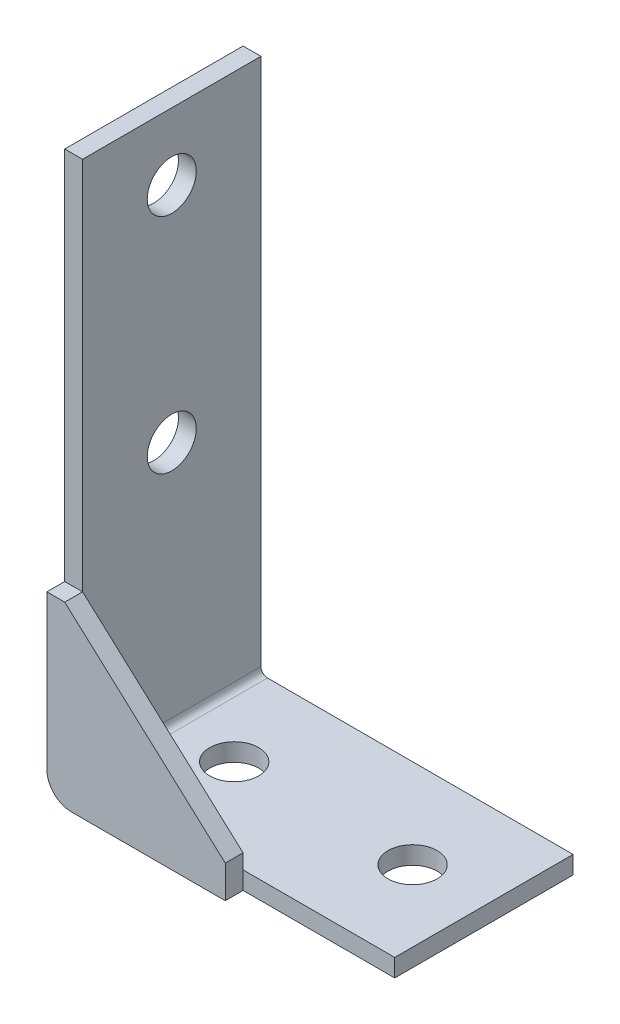
SolidWorks part; units mm, degrees
note: The reader was unsure of these and kept them because the rebuilt part matched: bend radius of "基体折弯1".
material "A3钢"
ref_plane "前视基准面" through (0, 0, 0) normal (0, 0, 1) x (1, 0, 0)
ref_plane "上视基准面" through (0, 0, 0) normal (0, 1, 0) x (1, 0, 0)
ref_plane "右视基准面" through (0, 0, 0) normal (1, 0, 0) x (0, 0, -1)
sketch "草图1" plane through (0, 0, 0) normal (0, 0, 1) x (1, 0, 0)
  line L0 (0, 60) -> (0, 0)
  line L1 (0, 0) -> (35, 0)
  dimension "D1" = 60
  dimension "D2" = 35
base flange "基体-法兰1" sketch "草图1" end condition mid plane depth 20 reverse direction no thickness 2 reverse thickness direction no bend radius 0.7366
bend "基体折弯1" bend radius 0.7366 bend angle 90 parameters "D5"=1
sketch "草图6" plane through (0, 0, 0) normal (0, 1, 0) x (1, 0, 0)
  line L0 (35, 0) -> (27, 0) construction
  line L1 (35, -10) -> (35, 10) construction
  line L2 (27, 0) -> (7, 0) construction
  dimension "D1" = 20
  dimension "D2" = 8
hole_wizard "Ø5.5 (5.5) 直径孔1" positions "3D草图1" profile "草图7" hole size "Ø5.5" standard "GB" end condition through all
sketch3d "3D草图1"
  point P0 (7, 0, 0)
  point P3 (27, 0, 0)
sketch "草图7" plane through (7, 0, 0) normal (1, 0, 0) x (0, 0, 1)
  line L0 (0, 0) -> (0, 2)
  line L1 (0, 2) -> (2.75, 2)
  line L2 (2.75, 2) -> (2.75, 0)
  line L5 (2.75, 0) -> (0, 0)
  line L11 (0, -6.35) -> (0, 107.95) construction
  dimension "通孔孔直径" = 5.5
  dimension "通孔孔深度" = 2
sketch "草图8" plane through (-2, 0, 0) normal (-1, 0, 0) x (0, 0, 1)
  line L0 (0, 60) -> (0, 52.5) construction
  line L1 (10, 60) -> (-10, 60) construction
  line L2 (0, 52.5) -> (0, 27.5) construction
  dimension "D1" = 25
  dimension "D2" = 7.5
hole_wizard "Ø5.5 (5.5) 直径孔2" positions "3D草图2" profile "草图10" hole size "Ø5.5" standard "GB" end condition through all
sketch3d "3D草图2"
  point P0 (-2, 52.5, 0)
  point P3 (-2, 27.5, 0)
sketch "草图10" plane through (-2, 52.5, 0) normal (0, 1, 0) x (0, 0, 1)
  line L0 (0, 0) -> (0, 37)
  line L1 (0, 37) -> (2.75, 37)
  line L2 (2.75, 37) -> (2.75, 0)
  line L5 (2.75, 0) -> (0, 0)
  line L11 (0, -6.35) -> (0, 107.95) construction
  dimension "通孔孔直径" = 5.5
  dimension "通孔孔深度" = 37
sketch "草图11" plane through (0, 0, 10) normal (0, 0, 1) x (1, 0, 0)
  line L0 (18, -2) -> (18, 1.6564)
  line L3 (18, 1.6564) -> (0, 18)
  line L4 (0, 60) -> (0, 0.7366) construction
  line L5 (0, 18) -> (-2, 18)
  line L6 (-2, 60) -> (-2, 0.7366) construction
  line L7 (-2, 18) -> (-2, 0.7366)
  line L8 (0.7366, -2) -> (35, -2) construction
  line L9 (0.7366, -2) -> (18, -2)
  arc A0 (-2, 0.7366) -> (0.7366, -2) centre (0.7366, 0.7366) ccw
  dimension "D1" = 20
  dimension "D2" = 20
base flange "基体-法兰2" sketch "草图11" thickness 2 reverse thickness direction yes parameters "D1"=0.7366
sketch "折弯-线1" [suppressed] plane through (0, 0, 0) normal (0, 1, 0) x (1, 0, 0)
sketch "边界框1" [suppressed] plane through (0, 0, 0) normal (0, 1, 0) x (1, 0, 0)
sheet metal parameters "钣金8" thickness 2 parameters "D1"=0.7366
flat pattern "平板型式8" [suppressed]
sketch "折弯-线2" plane through (0, 0, 0) normal (0, 1, 0) x (1, 0, 0)
  line L0 (-0.6273, -10) -> (-0.6273, 10) construction
  line L1 (-0.6273, -10) -> (-0.6273, 10) construction
sketch3d "边界框2" [suppressed]
  line L0 (35, 0, 0) -> (-36.2546, 0, 0) construction
  line L1 (35, 20, 0) -> (-36.2546, 20, 0) construction
  line L2 (35, 0, 0) -> (35, 20, 0) construction
  line L3 (-36.2546, 0, 0) -> (-36.2546, 20, 0) construction
bend of the flat pattern "展开-<基体折弯1>1"
sheet metal parameters "钣金9" thickness 2 parameters "D1"=0.7366
flat pattern "平板型式8" [suppressed]
sketch "折弯-线2" plane through (0, 0, 0) normal (0, 1, 0) x (1, 0, 0)
  line L0 (-0.6273, -10) -> (-0.6273, 10) construction
  line L1 (-0.6273, -10) -> (-0.6273, 10) construction
sketch3d "边界框2" [suppressed]
  line L0 (35, 0, 0) -> (-71.2546, 0, 0) construction
  line L1 (35, 20, 0) -> (-71.2546, 20, 0) construction
  line L2 (35, 0, 0) -> (35, 20, 0) construction
  line L3 (-71.2546, 0, 0) -> (-71.2546, 20, 0) construction
bend of the flat pattern "展开-<基体折弯1>1"
sketch "草图8-1" [suppressed] plane through (-1.2546, -2, 0) normal (0, -1, 0) x (0, 0, 1)
  line L0 (0, 70) -> (0, 55) construction
  line L2 (0, 55) -> (0, 35) construction
  dimension "D1" = 20
  dimension "D2" = 15
sheet metal parameters "钣金10" thickness 2 parameters "D1"=0.7366
flat pattern "平板型式8" [suppressed]
sketch "折弯-线2" plane through (0, 0, 0) normal (0, 1, 0) x (1, 0, 0)
  line L0 (-0.6273, -10) -> (-0.6273, 10) construction
  line L1 (-0.6273, -10) -> (-0.6273, 10) construction
sketch3d "边界框2" [suppressed]
  line L0 (35, 0, 0) -> (-61.2546, 0, 0) construction
  line L1 (35, 20, 0) -> (-61.2546, 20, 0) construction
  line L2 (35, 0, 0) -> (35, 20, 0) construction
  line L3 (-61.2546, 0, 0) -> (-61.2546, 20, 0) construction
bend of the flat pattern "展开-<基体折弯1>1"
sketch "草图8-1" plane through (-1.2546, -2, 0) normal (0, -1, 0) x (0, 0, 1)
  line L0 (0, 60) -> (0, 52.5) construction
  line L2 (0, 52.5) -> (0, 27.5) construction
  dimension "D1" = 25
  dimension "D2" = 7.5
sheet metal parameters "钣金11" thickness 2 parameters "D1"=0.7366
flat pattern "平板型式11"
sketch "折弯-线3" plane through (0, 0, 0) normal (0, 1, 0) x (1, 0, 0)
sketch3d "边界框3" [suppressed]
  line L0 (2.7366, -2.7366, 0) -> (-17.2634, -2.7366, 0) construction
  line L1 (2.7366, 17.2634, 0) -> (-17.2634, 17.2634, 0) construction
  line L2 (2.7366, -2.7366, 0) -> (2.7366, 17.2634, 0) construction
  line L3 (-17.2634, -2.7366, 0) -> (-17.2634, 17.2634, 0) construction
